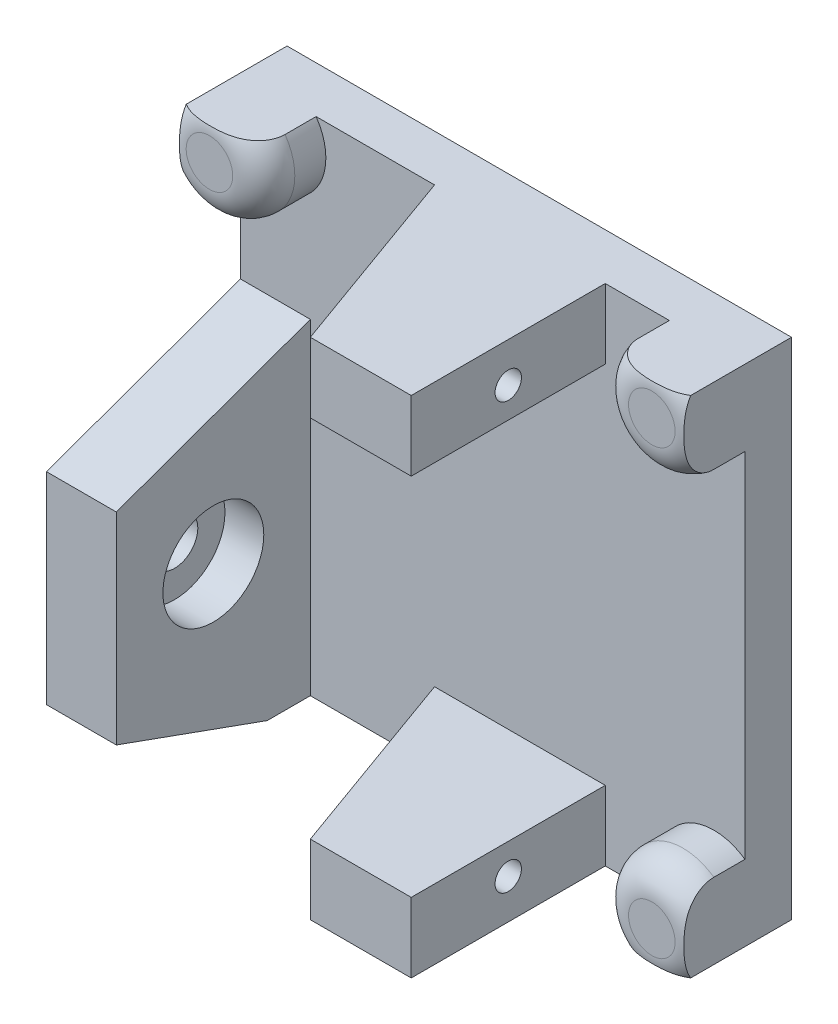
SolidWorks part; units mm, degrees
ref_plane "Спереди" through (0, 0, 0) normal (0, 0, 1) x (1, 0, 0)
ref_plane "Сверху" through (0, 0, 0) normal (0, 1, 0) x (1, 0, 0)
ref_plane "Справа" through (0, 0, 0) normal (1, 0, 0) x (0, 0, -1)
sketch "Эскиз2" plane through (0, 0, 0) normal (0, 0, 1) x (1, 0, 0)
  line L0 (9.5, 16.25) -> (-14, 16.25)
  line L2 (-14, 16.25) -> (-14, -16.25)
  line L3 (-14, -16.25) -> (9.5, -16.25)
  line L5 (9.5, -16.25) -> (9.5, -11.75)
  line L6 (9.5, -11.75) -> (-9.5, -11.75)
  line L8 (-9.5, 11.75) -> (9.5, 11.75)
  line L9 (9.5, 11.75) -> (9.5, 16.25)
  line L12 (-9.5, 11.75) -> (-9.5, -11.75)
  point P4 (-9.5, 0)
  point P6 (0, -11.75)
  dimension "D1" = 19
  dimension "D2" = 4.5
  dimension "D3" = 23.5
  dimension "D4" = 4.5
extrude "крепление сервы" add sketch "Эскиз2" along normal mid plane 12.5 separate body
sketch "Ы" plane through (9.5, 0, 0) normal (1, 0, 0) x (0, 0, -1)
  line L0 (0, 13.7) -> (0, -13.7) construction
  line L3 (-6.25, -11.75) -> (6.25, -11.75) construction
  circle A0 centre (0, 13.7) radius 0.85
  circle A1 centre (0, -13.7) radius 0.85
  point P0 (0, 0)
  point P8 (0, -11.75)
  dimension "D1" = 1.7
  dimension "D2" = 27.4
extrude "отверстие под саморез" cut sketch "Ы" against normal blind 5.5
sketch "Эскиз5" plane through (0, -11.75, 0) normal (0, -1, 0) x (1, 0, 0)
  line L0 (-14, 6.25) -> (9.5, 6.25) construction
  line L1 (-5.45, 6.25) -> (-2.95, 6.25)
  line L2 (-5.45, 6.25) -> (-5.45, -1.75)
  line L3 (-5.45, -1.75) -> (-2.95, -1.75)
  line L4 (-2.95, 6.25) -> (-2.95, -1.75)
  line L5 (9.5, 6.25) -> (9.5, -6.25) construction
  dimension "D1" = 2.5
  dimension "D2" = 12.45
  dimension "D3" = 8
extrude "паз для проводов" cut sketch "Эскиз5" along normal up to surface (4.5 mm away) up to face at (-2.25, -16.25, 0)
sketch "Эскиз1" plane through (0, 0, -6.25) normal (0, 0, -1) x (-1, 0, 0)
  line L0 (-19.5, 16) -> (-19.5, -18.1869) construction
  line L6 (15, 16) -> (15, -18.1869) construction
  line L7 (-16.5, 14.25) -> (12, 14.25) construction
  line L8 (-16.5, 14.25) -> (-16.5, -14.25) construction
  line L9 (-16.5, -14.25) -> (12, -14.25) construction
  line L10 (12, 14.25) -> (12, -14.25) construction
  line L11 (-18.5, 16.25) -> (14, 16.25)
  line L12 (-18.5, 16.25) -> (-18.5, -16.25)
  line L13 (-18.5, -16.25) -> (14, -16.25)
  line L14 (14, 16.25) -> (14, -16.25)
  line L15 (14, 16.25) -> (14, -16.25) construction
  line L16 (15, -18.1869) -> (-19.5, -18.1869) construction
  line L17 (2.95, -16.25) -> (-9.5, -16.25) construction
  point P0 (0, 0)
  point P14 (12, 0)
  point P15 (-2.25, 16.25)
  point P16 (-2.25, 14.25)
  point P17 (14, 0)
  point P28 (-2.25, -16.25)
  point P29 (-2.25, -18.1869)
  dimension "D1" = 28.5
  dimension "D5" = 1
extrude "Площадка под камеру" add sketch "Эскиз1" along normal blind 3
sketch "Эскиз4" plane through (-9.5, 0, 0) normal (1, 0, 0) x (0, 0, -1)
  line L0 (0, 11.75) -> (0, -11.75) construction
  line L1 (-6.25, 11.75) -> (6.25, 11.75) construction
  line L2 (-6.25, -11.75) -> (6.25, -11.75) construction
  circle A0 centre (0, -5.77) radius 1.5
  dimension "D1" = 3
  dimension "D2" = 5.77
extrude "отверстие под выход второй оси" cut sketch "Эскиз4" against normal through all
sketch "Эскиз8" [suppressed] plane through (0, 0, -6.25) normal (0, 0, -1) x (-1, 0, 0)
  line L0 (-2.25, 16.25) -> (-2.25, -16.25) construction
  line L1 (10.475, 17.31) -> (7.825, 15.78)
  line L2 (7.825, 15.78) -> (7.825, 12.72)
  line L3 (7.825, 12.72) -> (10.475, 11.19)
  line L4 (10.475, 11.19) -> (13.125, 12.72)
  line L5 (13.125, 12.72) -> (13.125, 15.78)
  line L6 (13.125, 15.78) -> (10.475, 17.31)
  line L7 (-18.5, 0) -> (14, 0) construction
  line L8 (14, 16.25) -> (-18.5, 16.25) construction
  line L9 (-18.5, -16.25) -> (14, -16.25) construction
  line L30 (14, -16.25) -> (14, 16.25) construction
  line L31 (-18.5, 16.25) -> (-18.5, -16.25) construction
  line L54 (-17.625, 15.78) -> (-14.975, 17.31)
  line L55 (-17.625, 12.72) -> (-17.625, 15.78)
  line L56 (-14.975, 11.19) -> (-17.625, 12.72)
  line L57 (-12.325, 12.72) -> (-14.975, 11.19)
  line L58 (-12.325, 15.78) -> (-12.325, 12.72)
  line L59 (-14.975, 17.31) -> (-12.325, 15.78)
  line L60 (-14.975, -17.31) -> (-12.325, -15.78)
  line L61 (-12.325, -15.78) -> (-12.325, -12.72)
  line L62 (-12.325, -12.72) -> (-14.975, -11.19)
  line L63 (-14.975, -11.19) -> (-17.625, -12.72)
  line L64 (-17.625, -12.72) -> (-17.625, -15.78)
  line L65 (-17.625, -15.78) -> (-14.975, -17.31)
  line L66 (13.125, -15.78) -> (10.475, -17.31)
  line L67 (13.125, -12.72) -> (13.125, -15.78)
  line L68 (10.475, -11.19) -> (13.125, -12.72)
  line L69 (7.825, -12.72) -> (10.475, -11.19)
  line L70 (7.825, -15.78) -> (7.825, -12.72)
  line L71 (10.475, -17.31) -> (7.825, -15.78)
  circle A1 centre (10.475, 14.25) radius 2.65 construction
  circle A2 centre (-14.975, 14.25) radius 2.65 construction
  circle A3 centre (-14.975, -14.25) radius 2.65 construction
  circle A4 centre (10.475, -14.25) radius 2.65 construction
  point P47 (-2.25, 0)
  point P48 (-2.25, 0)
  dimension "D1" = 5.3
extrude "Углубления под гайки" [suppressed] cut sketch "Эскиз8" along normal blind 4 contours L57 L56 L55 L54 L59 L58 | L1 L2 L3 L4 L5 L6 | L66 L71 L70 L69 L68 L67 | L60 L61 L62 L63 L64 L65
sketch "Эскиз6" [suppressed] plane through (0, 0, -6) normal (0, 0, 1) x (1, 0, 0)
  line L0 (0, 16.75) -> (0, -16.75) construction
  line L4 (-14.25, -14.25) -> (14.25, -14.25) construction
  line L5 (-14.25, -14.25) -> (-14.25, 14.25) construction
  line L6 (-14.25, 14.25) -> (14.25, 14.25) construction
  line L7 (14.25, -14.25) -> (14.25, 14.25) construction
  line L8 (-14.25, -14.25) -> (14.25, 14.25) construction
  line L9 (-14.25, 14.25) -> (14.25, -14.25) construction
  circle A0 centre (-14.25, 14.25) radius 1.1
  circle A1 centre (14.25, 14.25) radius 1.1
  circle A2 centre (14.25, -14.25) radius 1.1
  circle A3 centre (-14.25, -14.25) radius 1.1
  point P6 (0, 0)
  dimension "D1" = 2.2
  dimension "D3" = 28.5
extrude "крепление камеры (большой)" [suppressed] cut sketch "Эскиз6" against normal through all
chamfer "Фаска2" [suppressed] distance 1 angle 45
fillet "Скругление1" [suppressed] radius 2
fillet "Скругление2" [suppressed] radius 3 tangent propagation no
sketch "Эскиз9" plane through (0, 0, -9.25) normal (0, 0, -1) x (-1, 0, 0)
  line L0 (-11.75, 0) -> (7.25, 0) construction
  line L1 (14, 16.25) -> (-18.5, 16.25) construction
  line L2 (14, -16.25) -> (14, 16.25) construction
  circle A0 centre (-11.75, 0) radius 2.5
  circle A1 centre (7.25, 0) radius 2.5
  point P4 (-2.25, 0)
  point P7 (-2.25, 16.25)
  point P10 (14, 0)
  dimension "D1" = 5
  dimension "D2" = 19
extrude "Углубления под болты камеры" cut sketch "Эскиз9" against normal blind 2.5
fillet "Скругление3" radius 2.5 2 edges at (-9.75, 0, -6.75) (9.25, 0, -6.75)
sketch "Эскиз10" plane through (0, 16.25, 0) normal (0, 1, 0) x (1, 0, 0)
  line L0 (-9.5, -6.25) -> (-9.5, 6.25) construction
  line L1 (-9.5, 6.25) -> (3, 6.25)
  line L2 (-9.5, 6.25) -> (-9.5, -6.25)
  line L3 (-9.5, -6.25) -> (3, -6.25)
  line L4 (3, 6.25) -> (3, -6.25)
  line L5 (9.5, -6.25) -> (-14, -6.25) construction
  line L7 (9.5, -6.25) -> (9.5, 6.25) construction
  line L8 (-9.5, 6.25) -> (9.5, 6.25) construction
  dimension "D1" = 6.5
extrude "Срез боковых стенок для облегченной версии" cut sketch "Эскиз10" against normal through all
sketch "Эскиз13" plane through (-14, 0, 0) normal (-1, 0, 0) x (0, 0, 1)
  line L0 (-6.25, -16.25) -> (-6.25, 16.25) construction
  line L1 (-6.25, 16.25) -> (6.25, 16.25)
  line L2 (-6.25, 16.25) -> (-6.25, 0.25)
  line L3 (-6.25, 0.25) -> (6.25, 0.25)
  line L4 (6.25, 16.25) -> (6.25, 0.25)
  line L5 (6.25, 16.25) -> (6.25, -16.25) construction
  line L7 (-6.25, -12.75) -> (6.25, -12.75)
  line L8 (-6.25, -12.75) -> (-6.25, -16.25)
  line L9 (-6.25, -16.25) -> (6.25, -16.25)
  line L10 (6.25, -12.75) -> (6.25, -16.25)
  dimension "D3" = 3.5
  dimension "D1" = 16
extrude "Срез задней стенки под серву для облегченной версии" cut sketch "Эскиз13" against normal up to next
chamfer "Фаска3" distance 12.5 distance2 4.5 3 edges at (3, 14, -6.25) (3, -14, -6.25) (-11.75, -12.75, -6.25) first distance on face at (3, 14, 0) first distance on face at (3, -14, 0) first distance on face at (-11.75, -12.75, 0)
chamfer "Фаска4" distance 4.5 distance2 12.5 1 edges at (-11.75, 0.25, -6.25) first distance on face at (1.5714, 0.0357, -6.25)
sketch "Эскиз15" plane through (0, 0, -9.25) normal (0, 0, -1) x (-1, 0, 0)
  line L1 (-16.5, 14.25) -> (12, 14.25) construction
  line L2 (-16.5, 14.25) -> (-16.5, -14.25) construction
  line L3 (-16.5, -14.25) -> (12, -14.25) construction
  line L4 (12, 14.25) -> (12, -14.25) construction
  line L5 (-18.5, -16.25) -> (14, -16.25) construction
  line L6 (-18.5, 16.25) -> (-18.5, -16.25) construction
  circle A0 centre (12, -14.25) radius 0.75
  circle A1 centre (12, 14.25) radius 0.75
  circle A2 centre (-16.5, 14.25) radius 0.75
  circle A3 centre (-16.5, -14.25) radius 0.75
  point P8 (-2.25, -14.25)
  point P11 (-2.25, -16.25)
  point P12 (-16.5, 0)
  point P15 (-18.5, 0)
  dimension "D2" = 1.5
  dimension "D1" = 28.5
extrude "Отверстия шурупы для крепления камеры" cut sketch "Эскиз15" against normal blind 7
sketch "Эскиз16" plane through (0, 0, -6.25) normal (0, 0, 1) x (1, 0, 0)
  line L0 (16.5, 14.25) -> (-12, -14.25) construction
  line L1 (-14, 11.3777) -> (-14, 16.25)
  line L2 (-14, 16.25) -> (-14, 4.75) construction
  line L3 (-14, 16.25) -> (-9.1277, 16.25)
  line L4 (-1.5, 16.25) -> (-14, 16.25) construction
  line L12 (-12, 14.25) -> (16.5, -14.25) construction
  line L13 (13.6277, 16.25) -> (18.5, 16.25)
  line L14 (18.5, 16.25) -> (18.5, 11.3777)
  line L15 (18.5, -11.3777) -> (18.5, -16.25)
  line L16 (18.5, -16.25) -> (13.6277, -16.25)
  line L19 (-9.1277, -16.25) -> (-14, -16.25) [skipped]
  line L20 (-14, -16.25) -> (-14, -11.3777) [skipped]
  arc A5 (-14, 11.3777) -> (-9.1277, 16.25) centre (-12, 14.25) ccw
  circle A6 centre (-12, 14.25) radius 0.75 construction
  arc A7 (13.6277, 16.25) -> (18.5, 11.3777) centre (16.5, 14.25) ccw
  arc A8 (18.5, -11.3777) -> (13.6277, -16.25) centre (16.5, -14.25) ccw
  arc A10 (-9.1277, -16.25) -> (-14, -11.3777) centre (-12, -14.25) ccw [skipped]
  point P3 (2.25, 0)
  point P32 (2.25, 0)
  dimension "D1" = 3.5
  dimension "D2" = 4
extrude "Наплывы под шурупы" add sketch "Эскиз16" along normal blind 4
fillet "Скругление4" radius 2 3 edges at (14.0251, 11.7751, -2.25) (-9.5251, 11.7751, -2.25) (14.0251, -11.7751, -2.25)
sketch "Эскиз17" plane through (-9.5, 0, 0) normal (1, 0, 0) x (0, 0, -1)
  circle A0 centre (0, -5.77) radius 3.25
  dimension "D1" = 6.5
extrude "Углубление под шляпку болта  второй оси" cut sketch "Эскиз17" against normal blind 2.5
